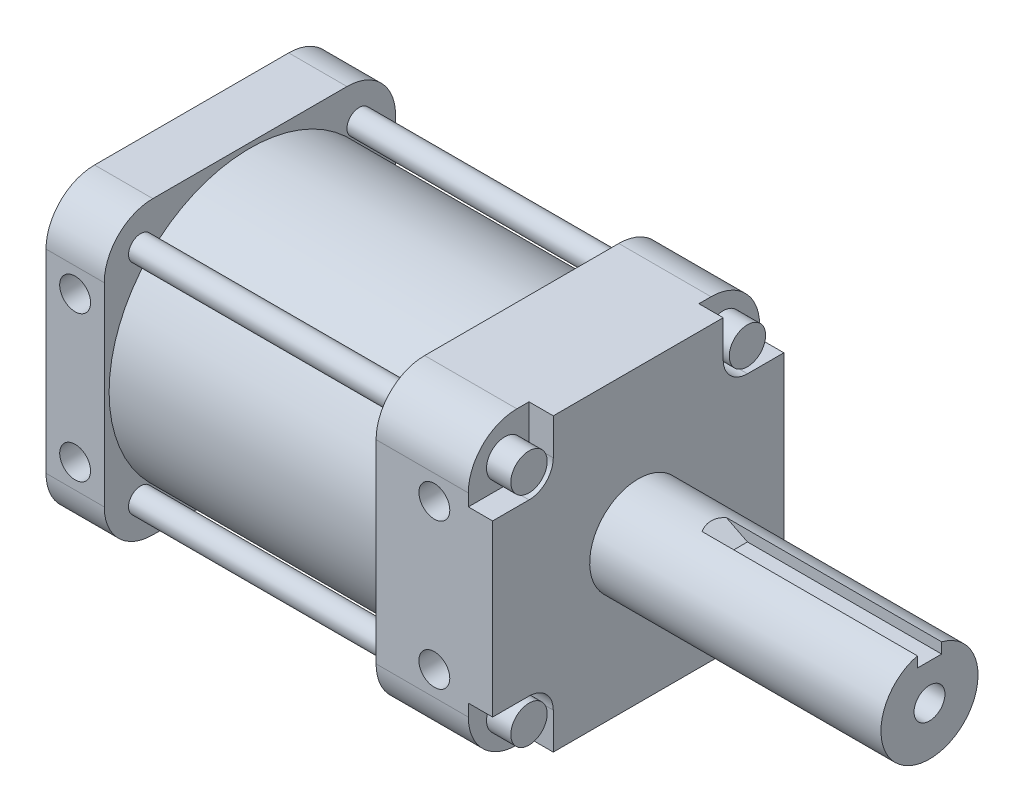
SolidWorks part; units mm, degrees
material "AISI 4130 Steel, normalized at 870C"
ref_plane "Front Plane" through (0, 0, 0) normal (0, 0, 1) x (1, 0, 0)
ref_plane "Top Plane" through (0, 0, 0) normal (0, 1, 0) x (1, 0, 0)
ref_plane "Right Plane" through (0, 0, 0) normal (1, 0, 0) x (0, 0, -1)
sketch "Sketch1" plane through (0, 0, 0) normal (1, 0, 0) x (0, 0, -1)
  line L0 (0, 19.05) -> (0, -19.05) construction
  line L1 (-12.7, 19.05) -> (12.7, 19.05)
  line L2 (-19.05, 12.7) -> (-19.05, -12.7)
  line L3 (-12.7, -19.05) -> (12.7, -19.05)
  line L4 (19.05, 12.7) -> (19.05, -12.7)
  arc A0 (12.7, 19.05) -> (19.05, 12.7) centre (12.7, 12.7) cw
  arc A1 (12.7, -19.05) -> (19.05, -12.7) centre (12.7, -12.7) ccw
  arc A2 (-19.05, -12.7) -> (-12.7, -19.05) centre (-12.7, -12.7) ccw
  arc A3 (-12.7, 19.05) -> (-19.05, 12.7) centre (-12.7, 12.7) ccw
  dimension "D2" = 6.35
  dimension "D1" = 38.1
extrude "Boss-Extrude1" add sketch "Sketch1" along normal blind 7.62
sketch "Sketch2" plane through (7.62, 0, 0) normal (1, 0, 0) x (0, 0, -1)
  circle A0 centre (0, 0) radius 18.415
  dimension "D1" = 36.83
extrude "Boss-Extrude2" add sketch "Sketch2" along normal blind 35.56
sketch "Sketch4" plane through (43.18, 0, 0) normal (1, 0, 0) x (0, 0, -1)
  line L0 (12.7, 19.05) -> (-12.7, 19.05) construction
  line L1 (-19.05, 12.7) -> (-19.05, -12.7) construction
  line L2 (-12.7, -19.05) -> (12.7, -19.05) construction
  line L3 (19.05, -12.7) -> (19.05, 12.7) construction
  line L4 (12.7, 19.05) -> (-12.7, 19.05)
  line L5 (-19.05, 12.7) -> (-19.05, -12.7)
  line L6 (-12.7, -19.05) -> (12.7, -19.05)
  line L7 (19.05, -12.7) -> (19.05, 12.7)
  arc A0 (-12.7, 19.05) -> (-19.05, 12.7) centre (-12.7, 12.7) ccw construction
  arc A1 (-19.05, -12.7) -> (-12.7, -19.05) centre (-12.7, -12.7) ccw construction
  arc A2 (12.7, -19.05) -> (19.05, -12.7) centre (12.7, -12.7) ccw construction
  arc A3 (19.05, 12.7) -> (12.7, 19.05) centre (12.7, 12.7) ccw construction
  arc A4 (-12.7, 19.05) -> (-19.05, 12.7) centre (-12.7, 12.7) ccw
  arc A5 (-19.05, -12.7) -> (-12.7, -19.05) centre (-12.7, -12.7) ccw
  arc A6 (12.7, -19.05) -> (19.05, -12.7) centre (12.7, -12.7) ccw
  arc A7 (19.05, 12.7) -> (12.7, 19.05) centre (12.7, 12.7) ccw
extrude "Boss-Extrude3" add sketch "Sketch4" along normal blind 15.24
sketch "Sketch5" plane through (58.42, 0, 0) normal (1, 0, 0) x (0, 0, -1)
  circle A0 centre (0, 0) radius 6.35
  dimension "D1" = 12.7
extrude "Boss-Extrude4" add sketch "Sketch5" along normal blind 38.1
hole_wizard "#10-32 Tapped Hole1" positions "3DSketch1" profile "Sketch6" tap size "#10-32" standard "ANSI Inch"
sketch3d "3DSketch1"
  line L18 (58.42, 0, -19.05) -> (43.18, 0, -19.05) construction
  line L19 (58.42, -12.7, -19.05) -> (58.42, 12.7, -19.05) construction
  line L20 (43.18, -12.7, -19.05) -> (43.18, 12.7, -19.05) construction
  line L23 (7.62, 0, -19.05) -> (0, 0, -19.05) construction
  line L24 (7.62, -12.7, -19.05) -> (7.62, 12.7, -19.05) construction
  line L25 (0, -12.7, -19.05) -> (0, 12.7, -19.05) construction
  line L28 (3.81, 9.525, -19.05) -> (3.81, 0, -19.05) construction
  line L31 (3.81, -9.525, -19.05) -> (3.81, 0, -19.05) construction
  line L34 (50.8, 9.525, -19.05) -> (50.8, 0, -19.05) construction
  line L35 (50.8, 0, -19.05) -> (50.8, -9.525, -19.05) construction
  point P35 (50.8, 9.525, -19.05)
  point P39 (50.8, -9.525, -19.05)
  point P41 (3.81, 9.525, -19.05)
  point P43 (3.81, -9.525, -19.05)
  point P45 (50.8, 9.525, 19.05)
  point P47 (50.8, -9.525, 19.05)
  point P49 (3.81, 9.525, 19.05)
  point P51 (3.81, -9.525, 19.05)
  dimension "D1" = 9.525
sketch "Sketch6" plane through (50.8, 9.525, -19.05) normal (1, 0, 0) x (0, 1, 0)
  line L0 (0, 0) -> (0, 8.8333)
  line L1 (0, 8.8333) -> (2.0193, 7.62)
  line L2 (2.0193, 7.62) -> (2.0193, 0)
  line L5 (2.0193, 0) -> (0, 0)
  line L10 (0, 8.8333) -> (-2.0193, 7.62) construction
  line L11 (0, -6.35) -> (0, 107.95) construction
  dimension "Tap Drill Dia." = 4.0386
  dimension "Tap Drill Depth" = 7.62
  dimension "Drill Angle" = 118
sketch "Sketch8" plane through (0, 0, 0) normal (-1, 0, 0) x (0, 0, 1)
  circle A0 centre (0, 0) radius 17.78
  dimension "D1" = 35.56
extrude "Cut-Extrude1" cut sketch "Sketch8" against normal blind 45.72 from offset 7.62 offset against normal yes
sketch "Sketch9" plane through (0, 0, 0) normal (-1, 0, 0) x (0, 0, 1)
  circle A0 centre (0, 0) radius 6
  dimension "D1" = 12
extrude "Cut-Extrude2" cut sketch "Sketch9" against normal up to next
sketch "Sketch10" plane through (0, 0, 0) normal (0, 0, 1) x (1, 0, 0)
  line L0 (96.52, 4.7625) -> (71.12, 4.7625)
  line L1 (96.52, -6.35) -> (96.52, 6.35) construction
  line L2 (71.12, 4.7625) -> (67.945, 6.35)
  line L3 (96.52, 6.35) -> (58.42, 6.35) construction
  line L4 (67.945, 6.35) -> (96.52, 6.35)
  line L5 (96.52, 6.35) -> (96.52, 4.7625)
  dimension "D1" = 1.5875
  dimension "D2" = 3.175
  dimension "D3" = 25.4
extrude "Cut-Extrude3" cut sketch "Sketch10" against normal mid plane 3.175
hole_wizard "#10-32 Tapped Hole2" positions "Sketch12" profile "Sketch11" tap size "#10-32" standard "ANSI Inch"
sketch "Sketch12" plane through (96.52, 0, 0) normal (1, 0, 0) x (0, 0, -1)
  point P0 (0, 0)
sketch "Sketch11" plane through (96.52, 0, 0) normal (0, 1, 0) x (0, 0, -1)
  line L0 (0, 0) -> (0, 8.8333)
  line L1 (0, 8.8333) -> (2.0193, 7.62)
  line L2 (2.0193, 7.62) -> (2.0193, 0)
  line L5 (2.0193, 0) -> (0, 0)
  line L10 (0, 8.8333) -> (-2.0193, 7.62) construction
  line L11 (0, -6.35) -> (0, 107.95) construction
  dimension "Tap Drill Dia." = 4.0386
  dimension "Tap Drill Depth" = 7.62
  dimension "Drill Angle" = 118
sketch "Sketch14" plane through (58.42, 0, 0) normal (1, 0, 0) x (0, 0, -1)
  line L0 (-14.2875, 11.1125) -> (-19.05, 11.1125)
  line L1 (-19.05, 12.7) -> (-19.05, -12.7) construction
  line L2 (-11.1125, 14.2875) -> (-11.1125, 19.05)
  line L3 (12.7, 19.05) -> (-12.7, 19.05) construction
  line L4 (-14.2875, -11.1125) -> (-19.05, -11.1125)
  line L5 (-11.1125, -14.2875) -> (-11.1125, -19.05)
  line L6 (-12.7, -19.05) -> (12.7, -19.05) construction
  line L7 (11.1125, 14.2875) -> (11.1125, 19.05)
  line L8 (14.2875, 11.1125) -> (19.05, 11.1125)
  line L9 (19.05, -12.7) -> (19.05, 12.7) construction
  line L10 (14.2875, -11.1125) -> (19.05, -11.1125)
  line L11 (11.1125, -14.2875) -> (11.1125, -19.05)
  line L12 (-19.05, 11.1125) -> (-19.05, 19.05)
  line L13 (-19.05, 19.05) -> (-11.1125, 19.05)
  line L14 (11.1125, 19.05) -> (19.05, 19.05)
  line L15 (19.05, 19.05) -> (19.05, 11.1125)
  line L16 (19.05, -11.1125) -> (19.05, -19.05)
  line L17 (19.05, -19.05) -> (11.1125, -19.05)
  line L18 (-11.1125, -19.05) -> (-19.05, -19.05)
  line L19 (-19.05, -19.05) -> (-19.05, -11.1125)
  arc A0 (-14.2875, 11.1125) -> (-11.1125, 14.2875) centre (-14.2875, 14.2875) ccw
  arc A1 (11.1125, 14.2875) -> (14.2875, 11.1125) centre (14.2875, 14.2875) ccw
  arc A2 (14.2875, -11.1125) -> (11.1125, -14.2875) centre (14.2875, -14.2875) ccw
  arc A3 (-11.1125, -14.2875) -> (-14.2875, -11.1125) centre (-14.2875, -14.2875) ccw
  dimension "D2" = 3.175
  dimension "D1" = 7.9375
extrude "Cut-Extrude4" cut sketch "Sketch14" against normal blind 3.175
sketch "Sketch15" plane through (43.18, 0, 0) normal (-1, 0, 0) x (0, 0, 1)
  circle A0 centre (14.2875, 14.2875) radius 1.5875
  circle A1 centre (-14.2875, 14.2875) radius 1.5875
  circle A2 centre (14.2875, -14.2875) radius 1.5875
  circle A3 centre (-14.2875, -14.2875) radius 1.5875
  dimension "D1" = 3.175
extrude "Boss-Extrude5" add sketch "Sketch15" along normal up to next
sketch "Sketch16" plane through (55.245, 0, 0) normal (1, 0, 0) x (0, 0, -1)
  circle A0 centre (-14.2875, 14.2875) radius 2.3813
  circle A1 centre (-14.2875, -14.2875) radius 2.3813
  circle A2 centre (14.2875, -14.2875) radius 2.3813
  circle A3 centre (14.2875, 14.2875) radius 2.3813
  dimension "D1" = 4.7625
extrude "Boss-Extrude6" add sketch "Sketch16" along normal blind 3.175
